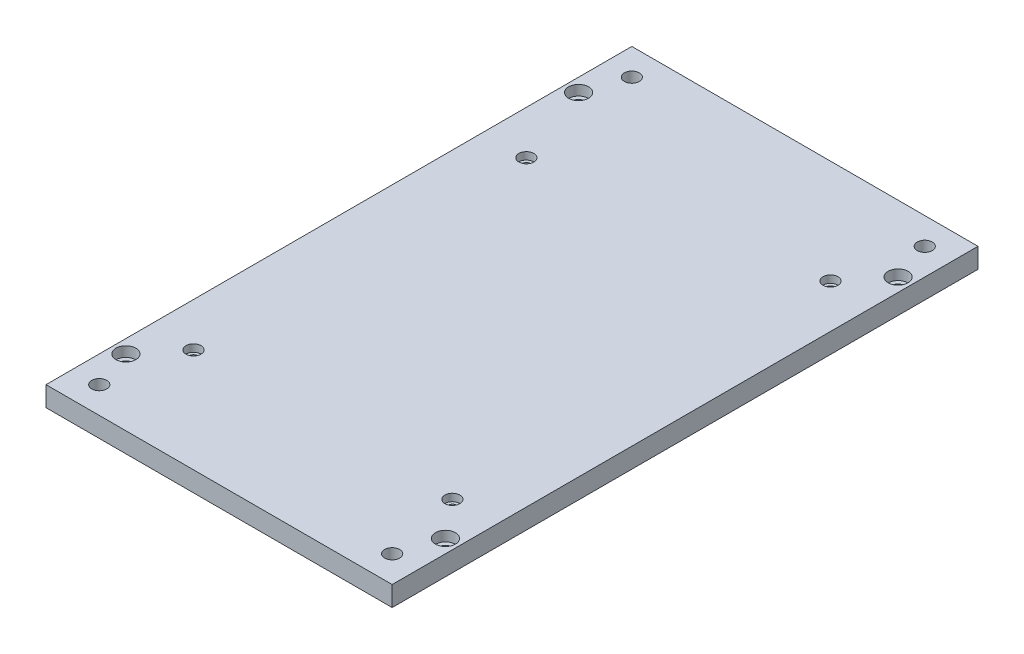
SolidWorks part; units mm, degrees
note: '?' marks a value the reader was unsure of.
material "6061 Alloy"
ref_plane "Front Plane" through (0, 0, 0) normal (0, 0, 1) x (1, 0, 0)
ref_plane "Top Plane" through (0, 0, 0) normal (0, 1, 0) x (1, 0, 0)
ref_plane "Right Plane" through (0, 0, 0) normal (1, 0, 0) x (0, 0, -1)
sketch "Sketch1" plane through (0, 0, 0) normal (0, 1, 0) x (1, 0, 0)
  line L1 (0, 0) -> (165.1, 0)
  line L2 (0, 0) -> (0, 279.4)
  line L3 (0, 279.4) -> (165.1, 279.4)
  line L4 (165.1, 0) -> (165.1, 279.4)
  dimension "D1" = 279.4
  dimension "D2" = 165.1
extrude "Boss-Extrude1" add sketch "Sketch1" along normal blind 9.525 contours L2 L3 L4 L1
ref_axis "Axis1" through (82.55, 9.525, -279.4) along (0, 0, 1)?
ref_axis "Axis2" through (165.1, 9.525, -139.7) along (-1, 0, 0)?
hole_wizard "1/4 Clearance Hole1" positions "Sketch2" profile "Sketch3" hole size "1/4" standard "ANSI Inch" end condition up to next
sketch "Sketch2" plane through (0, 9.525, 0) normal (0, 1, 0) x (1, 0, 0)
  line L0 (152.4, 12.7) -> (152.4, 266.7)
  line L1 (152.4, 266.7) -> (12.7, 266.7)
  line L2 (12.7, 266.7) -> (12.7, 12.7)
  line L3 (12.7, 12.7) -> (152.4, 12.7)
  line L5 (165.1, 139.7) -> (0, 139.7) construction
  line L6 (82.55, 279.4) -> (82.55, 0) construction
  line L7 (0, 0) -> (0, 279.4) construction
  line L8 (0, 0) -> (165.1, 0) construction
  point P0 (152.4, 12.7)
  point P2 (12.7, 12.7)
  point P4 (12.7, 266.7)
  point P6 (152.4, 266.7)
  point P19 (152.4, 139.7)
  point P22 (82.55, 12.7)
  dimension "D1" = 12.7
  dimension "D2" = 12.7
sketch "Sketch3" plane through (152.4, 9.525, -12.7) normal (1, 0, 0) x (0, 0, 1)
  line L0 (0, 0) -> (0, 9.525)
  line L1 (0, 9.525) -> (3.5712, 9.525)
  line L2 (3.5712, 9.525) -> (3.5712, 0)
  line L5 (3.5712, 0) -> (0, 0)
  line L11 (0, -6.35) -> (0, 107.95) construction
  dimension "Thru Hole Dia." = 7.1425
  dimension "Thru Hole Depth" = 9.525
hole_wizard "CBORE for #10 Socket Head Cap Screw1" positions "Sketch4" profile "Sketch5" counterbore size "#10" standard "ANSI Inch"
sketch "Sketch4" plane through (0, 9.525, 0) normal (0, 1, 0) x (1, 0, 0)
  line L0 (165.1, 139.7) -> (0, 139.7) construction
  line L1 (158.75, 139.7) -> (158.75, 247.65)
  line L2 (158.75, 247.65) -> (6.35, 247.65)
  line L3 (6.35, 247.65) -> (6.35, 139.7)
  line L4 (6.35, 139.7) -> (6.35, 31.75)
  line L5 (6.35, 31.75) -> (158.75, 31.75)
  line L6 (158.75, 31.75) -> (158.75, 139.7)
  line L8 (82.55, 279.4) -> (82.55, 0) construction
  line L9 (165.1, 0) -> (165.1, 279.4) construction
  point P0 (158.75, 139.7)
  point P2 (6.35, 139.7)
  point P4 (6.35, 31.75)
  point P6 (158.75, 31.75)
  point P8 (158.75, 247.65)
  point P10 (6.35, 247.65)
  point P31 (82.55, 31.75)
  dimension "D1" = 6.35
  dimension "D2" = 215.9
sketch "Sketch5" plane through (6.35, 9.525, -247.65) normal (1, 0, 0) x (0, 0, 1)
  line L0 (0, 0) -> (0, 9.525)
  line L1 (0, 9.525) -> (2.8067, 9.525)
  line L3 (2.8067, 9.525) -> (2.8067, 4.826)
  line L4 (2.8067, 4.826) -> (4.7625, 4.826)
  line L5 (4.7625, 4.826) -> (4.7625, 0)
  line L7 (4.7625, 0) -> (0, 0)
  line L11 (0, -6.35) -> (0, 107.95) construction
  dimension "Thru Hole Dia." = 5.6134
  dimension "Thru Hole Depth" = 9.525
  dimension "C'Bore Dia." = 9.525
  dimension "C'Bore Depth" = 4.826
hole_wizard "CBORE for #6 Socket Head Cap Screw1" positions "Sketch8" profile "Sketch7" counterbore size "#6" standard "ANSI Inch" end condition up to next
sketch "Sketch8" plane through (0, 9.525, 0) normal (0, 1, 0) x (1, 0, 0)
  line L0 (144.272, 229.87) -> (144.272, 49.53)
  line L1 (144.272, 49.53) -> (20.828, 49.53)
  line L2 (20.828, 49.53) -> (20.828, 208.28)
  line L3 (20.828, 208.28) -> (20.828, 229.87)
  line L4 (20.828, 229.87) -> (144.272, 229.87)
  line L6 (165.1, 139.7) -> (0, 139.7) construction
  line L7 (82.55, 279.4) -> (82.55, 0) construction
  point P0 (144.272, 229.87)
  point P2 (144.272, 49.53)
  point P4 (20.828, 49.53)
  point P6 (20.828, 208.28)
  point P21 (144.272, 139.7)
  point P24 (82.55, 49.53)
  dimension "D1" = 123.444
  dimension "D2" = 180.34
  dimension "D3" = 158.75
sketch "Sketch7" plane through (144.272, 9.525, -229.87) normal (1, 0, 0) x (0, 0, 1)
  line L0 (0, 0) -> (0, 9.525)
  line L1 (0, 9.525) -> (2.1526, 9.525)
  line L3 (2.1526, 9.525) -> (2.1526, 3.5052)
  line L4 (2.1526, 3.5052) -> (3.5725, 3.5052)
  line L5 (3.5725, 3.5052) -> (3.5725, 0)
  line L7 (3.5725, 0) -> (0, 0)
  line L11 (0, -6.35) -> (0, 107.95) construction
  dimension "Thru Hole Dia." = 4.3053
  dimension "Thru Hole Depth" = 9.525
  dimension "C'Bore Dia." = 7.145
  dimension "C'Bore Depth" = 3.5052
